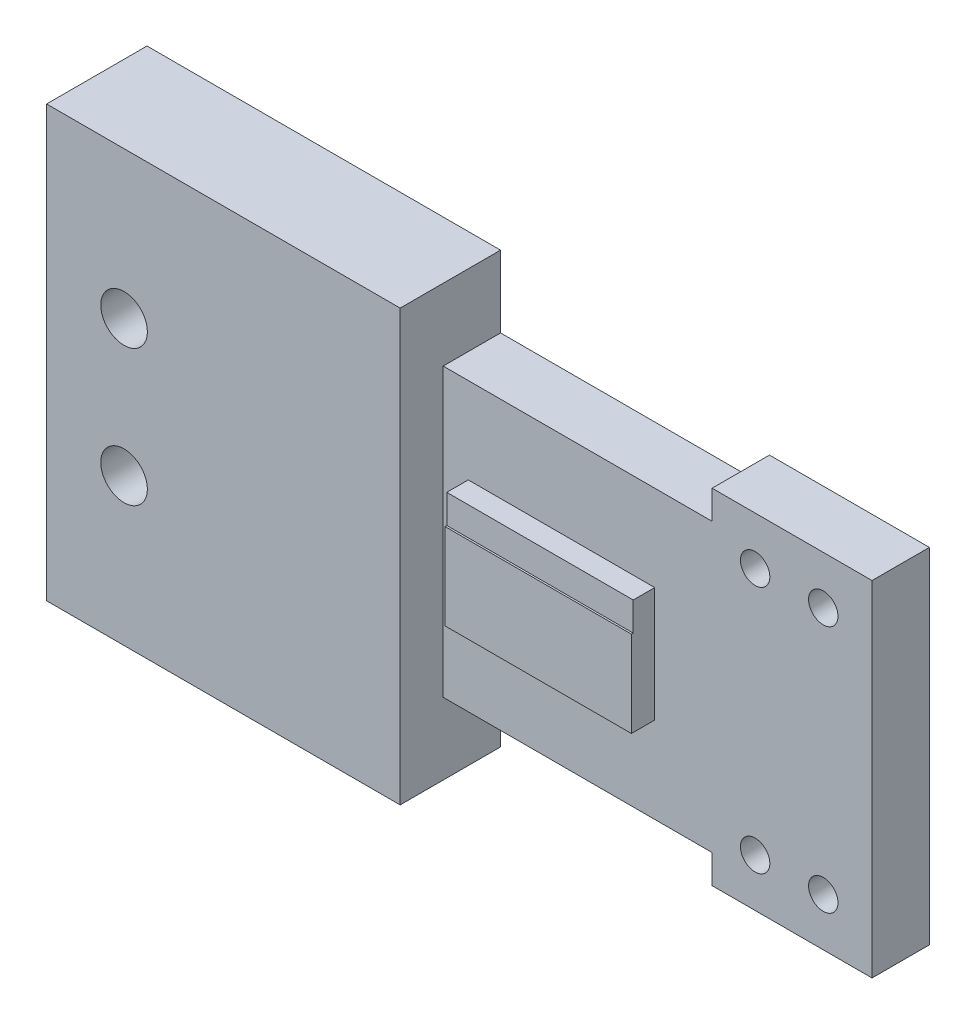
SolidWorks part; units mm, degrees
ref_plane "Front Plane" through (0, 0, 0) normal (0, 0, 1) x (1, 0, 0)
ref_plane "Top Plane" through (0, 0, 0) normal (0, 1, 0) x (1, 0, 0)
ref_plane "Right Plane" through (0, 0, 0) normal (1, 0, 0) x (0, 0, -1)
ref_plane "Plane1" through (0, 0, 246) normal (0, 0, 1) x (1, 0, 0)
sketch "Sketch1" plane through (0, 0, 246) normal (0, 0, 1) x (1, 0, 0)
  line L0 (227.2, 280) -> (336.3, 280)
  line L1 (336.3, 280) -> (336.3, 320)
  line L2 (336.3, 320) -> (227.2, 320)
  line L3 (227.2, 320) -> (227.2, 280)
  line L4 (290, 296) -> (290, 304)
  line L5 (286, 304) -> (286, 296)
  line L6 (304, 296) -> (304, 304)
  line L7 (300, 304) -> (300, 296)
  arc A0 (290, 304) -> (286, 304) centre (288, 304) ccw
  arc A1 (286, 296) -> (290, 296) centre (288, 296) ccw
  arc A2 (304, 304) -> (300, 304) centre (302, 304) ccw
  arc A3 (300, 296) -> (304, 296) centre (302, 296) ccw
extrude "Boss-Extrude1" add sketch "Sketch1" along normal blind 8
sketch "Sketch2" plane through (0, 0, 246) normal (0, 0, 1) x (1, 0, 0)
  line L0 (314, 276) -> (336.3, 276)
  line L1 (336.3, 276) -> (336.3, 324)
  line L2 (336.3, 324) -> (314, 324)
  line L3 (314, 324) -> (314, 276)
extrude "Boss-Extrude2" add sketch "Sketch2" along normal blind 8
sketch "Sketch3" plane through (0, 0, 246) normal (0, 0, 1) x (1, 0, 0)
  line L0 (227.2, 270) -> (276.5, 270)
  line L1 (276.5, 270) -> (276.5, 330)
  line L2 (276.5, 330) -> (227.2, 330)
  line L3 (227.2, 330) -> (227.2, 270)
extrude "Boss-Extrude3" add sketch "Sketch3" along normal blind 8
ref_plane "Plane2" through (0, 0, 254) normal (0, 0, 1) x (1, 0, 0)
sketch "Sketch4" plane through (0, 0, 254) normal (0, 0, 1) x (1, 0, 0)
  line L0 (227.2, 270) -> (276.5, 270)
  line L1 (276.5, 270) -> (276.5, 330)
  line L2 (276.5, 330) -> (227.2, 330)
  line L3 (227.2, 330) -> (227.2, 270)
extrude "Boss-Extrude4" add sketch "Sketch4" along normal blind 6
ref_plane "Plane3" through (0, 0, 248.9) normal (0, 0, 1) x (1, 0, 0)
sketch "Sketch5" plane through (0, 0, 248.9) normal (0, 0, 1) x (1, 0, 0)
  circle A0 centre (238, 290.5) radius 3.25
  circle A1 centre (238, 309.5) radius 3.25
extrude "Cut-Extrude1" cut sketch "Sketch5" along normal blind 11.1
sketch "Sketch6" plane through (0, 0, 246) normal (0, 0, 1) x (1, 0, 0)
  circle A0 centre (252, 281) radius 3.25
  circle A1 centre (252, 319) radius 3.25
  circle A2 centre (266, 281) radius 3.25
  circle A3 centre (266, 319) radius 3.25
extrude "Cut-Extrude2" cut sketch "Sketch6" along normal blind 11.1
ref_plane "Plane4" through (0, 0, 247.3) normal (0, 0, 1) x (1, 0, 0)
sketch "Sketch7" plane through (0, 0, 247.3) normal (0, 0, 1) x (1, 0, 0)
  circle A0 centre (320, 282.7) radius 2.05
  circle A1 centre (320, 317.3) radius 2.05
  circle A2 centre (329.5, 282.7) radius 2.05
  circle A3 centre (329.5, 317.3) radius 2.05
extrude "Cut-Extrude3" cut sketch "Sketch7" along normal blind 6.7
sketch "Sketch8" plane through (0, 0, 254) normal (0, 0, 1) x (1, 0, 0)
  line L0 (280, 292) -> (306, 292)
  line L1 (306, 292) -> (306, 304)
  line L2 (306, 304) -> (280, 304)
  line L3 (280, 304) -> (280, 292)
extrude "Boss-Extrude5" add sketch "Sketch8" along normal blind 3.25
sketch "Sketch9" plane through (0, 0, 254) normal (0, 0, 1) x (1, 0, 0)
  line L0 (280, 296) -> (306, 296)
  line L1 (306, 296) -> (306, 308)
  line L2 (306, 308) -> (280, 308)
  line L3 (280, 308) -> (280, 296)
extrude "Boss-Extrude6" add sketch "Sketch9" along normal blind 3
ref_plane "Plane5" through (0, 300, 0) normal (0, 1, 0) x (1, 0, 0)
ref_plane "Plane6" through (0, 0, 300) normal (0, 0, 1) x (1, 0, 0)
ref_axis "ABAD_AXIS" through (341.755, 300, 300) along (-1, 0, 0)
